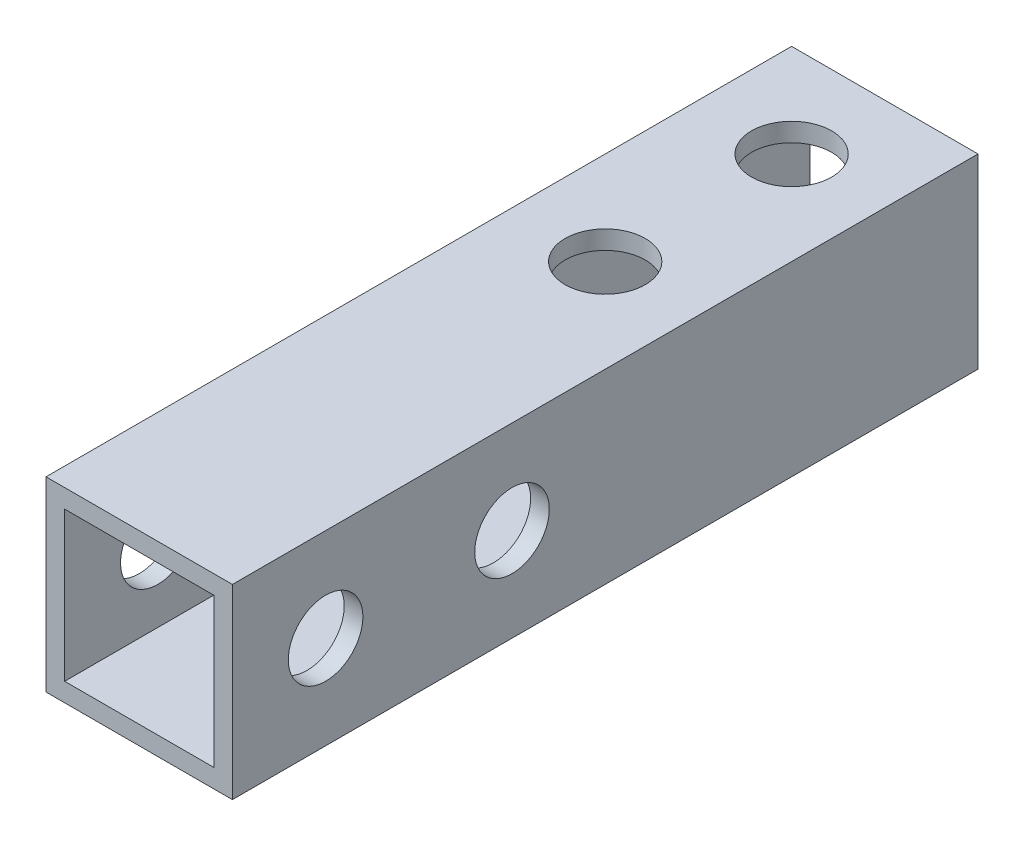
SolidWorks part; units mm, degrees
material "5052-H34"
ref_plane "正面" through (0, 0, 0) normal (0, 0, 1) x (1, 0, 0)
ref_plane "平面" through (0, 0, 0) normal (0, 1, 0) x (1, 0, 0)
ref_plane "右側面" through (0, 0, 0) normal (1, 0, 0) x (0, 0, -1)
sketch "ｽｹｯﾁ1" plane through (0, 0, 0) normal (0, 0, 1) x (1, 0, 0)
  line L1 (-5, 5) -> (5, 5)
  line L2 (-5, 5) -> (-5, -5)
  line L3 (-5, -5) -> (5, -5)
  line L4 (5, 5) -> (5, -5)
  line L5 (-5, 5) -> (5, -5) construction
  line L6 (-5, -5) -> (5, 5) construction
  point P0 (0, 0)
  dimension "D1" = 10
  dimension "D2" = 10
extrude "押し出し-薄板1" add sketch "ｽｹｯﾁ1" along normal blind 40 thin thin type one direction reverse wall 1
sketch "ｽｹｯﾁ2" plane through (0, 5, 0) normal (0, 1, 0) x (1, 0, 0)
  line L0 (0, 0) -> (0, -15) construction
  circle A0 centre (0, -15) radius 2.15
  circle A1 centre (0, -5) radius 2.15
  dimension "D1" = 4.3
  dimension "D2" = 5
  dimension "D3" = 10
extrude "ｶｯﾄ - 押し出し1" cut sketch "ｽｹｯﾁ2" against normal through all
sketch "ｽｹｯﾁ3" plane through (5, 0, 0) normal (1, 0, 0) x (0, 0, -1)
  line L1 (-20, 5) -> (-20, -5) construction
  line L2 (-40, 5) -> (0, 5) construction
  line L3 (-40, -5) -> (0, -5) construction
  line L5 (0, 0) -> (-25, 0) construction
  circle A2 centre (-25, 0) radius 2
  circle A3 centre (-35, 0) radius 2
  point P9 (0, 0)
  dimension "D1" = 4
  dimension "D2" = 10
  dimension "D3" = 25
extrude "ｶｯﾄ - 押し出し2" cut sketch "ｽｹｯﾁ3" against normal through all
